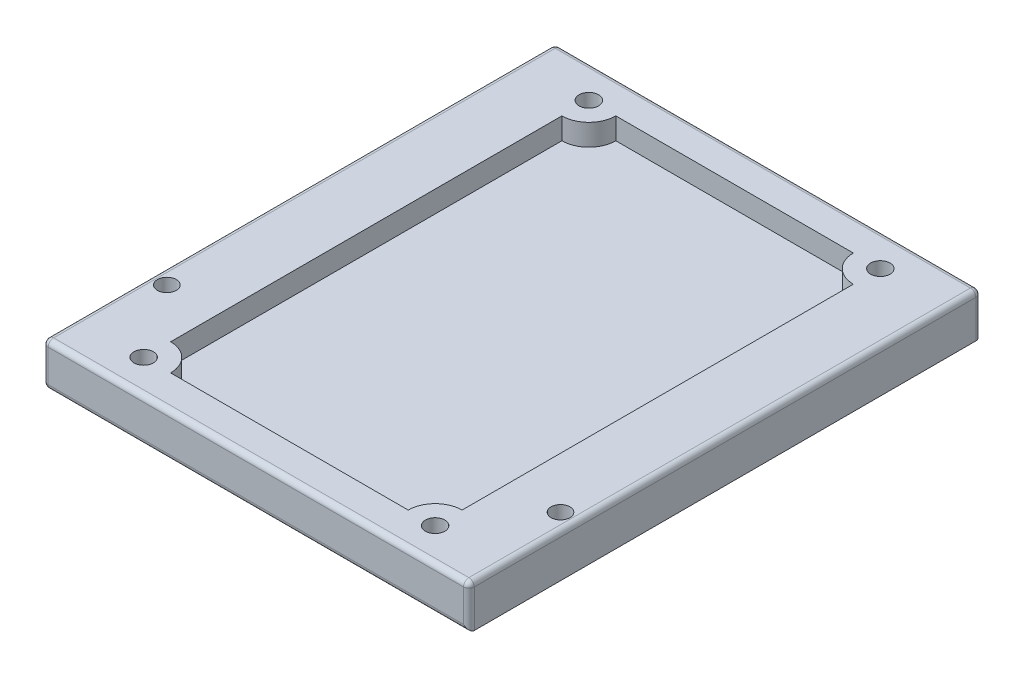
SolidWorks part; units mm, degrees
ref_plane "Front Plane" through (0, 0, 0) normal (0, 0, 1) x (1, 0, 0)
ref_plane "Top Plane" through (0, 0, 0) normal (0, 1, 0) x (1, 0, 0)
ref_plane "Right Plane" through (0, 0, 0) normal (1, 0, 0) x (0, 0, -1)
sketch "Sketch1" plane through (0, 0, 0) normal (0, 1, 0) x (1, 0, 0)
  line L0 (39.5, 95) -> (39.5, 0) construction
  line L1 (0, 0) -> (79, 0)
  line L2 (0, 0) -> (0, 95)
  line L3 (0, 95) -> (79, 95)
  line L4 (79, 0) -> (79, 95)
  circle A0 centre (3, 20) radius 1.75
  circle A1 centre (12.475, 6.225) radius 1.65 construction
  circle A2 centre (12.475, 88.775) radius 1.65 construction
  circle A3 centre (76, 20) radius 1.75
  circle A4 centre (66.525, 6.225) radius 1.65 construction
  circle A5 centre (66.525, 88.775) radius 1.65 construction
  point P20 (39.5, 0)
  dimension "D2" = 3
  dimension "D3" = 3.5
  dimension "D5" = 20
  dimension "D6" = 12.475
  dimension "D7" = 3.3
  dimension "D8" = 12.475
  dimension "D9" = 82.55
  dimension "D10" = 3.3
  dimension "D11" = 6.225
  dimension "D1" = 79
  dimension "D4" = 95
extrude "Boss-Extrude1" add sketch "Sketch1" along normal blind 8
sketch "Sketch3" plane through (0, 0, 0) normal (0, -1, 0) x (1, 0, 0)
  point P0 (12.475, -6.225)
  point P1 (66.525, -6.225)
  point P3 (66.525, -88.775)
  point P5 (12.475, -88.775)
hole_wizard "CBORE for M3 SHCS1" positions "Sketch3" profile "Sketch4" counterbore size "M3" standard "ANSI Metric" end condition through all
sketch "Sketch4" plane through (12.475, 0, -6.225) normal (1, 0, 0) x (0, 0, -1)
  line L0 (0, 0) -> (0, 8)
  line L1 (0, 8) -> (1.8, 8)
  line L3 (1.8, 8) -> (1.8, 3)
  line L4 (1.8, 3) -> (3.25, 3)
  line L5 (3.25, 3) -> (3.25, 0)
  line L7 (3.25, 0) -> (0, 0)
  line L11 (0, -6.35) -> (0, 107.95) construction
  dimension "Thru Hole Dia." = 3.6
  dimension "Thru Hole Depth" = 8
  dimension "C'Bore Dia." = 6.5
  dimension "C'Bore Depth" = 3
sketch "Sketch5" plane through (0, 8, 0) normal (0, 1, 0) x (1, 0, 0)
  line L1 (17.475, 88.775) -> (61.525, 88.775)
  line L2 (12.475, 83.775) -> (12.475, 11.225)
  line L3 (17.475, 6.225) -> (61.525, 6.225)
  line L4 (66.525, 83.775) -> (66.525, 11.225)
  circle A0 centre (12.475, 88.775) radius 1.65 construction
  circle A1 centre (12.475, 6.225) radius 1.65 construction
  arc A3 (12.475, 83.775) -> (17.475, 88.775) centre (12.475, 88.775) ccw
  arc A4 (61.525, 88.775) -> (66.525, 83.775) centre (66.525, 88.775) ccw
  arc A5 (66.525, 11.225) -> (61.525, 6.225) centre (66.525, 6.225) ccw
  arc A6 (17.475, 6.225) -> (12.475, 11.225) centre (12.475, 6.225) ccw
  dimension "D3" = 54.05
  dimension "D1" = 0
  dimension "D2" = 0
extrude "Cut-Extrude1" cut sketch "Sketch5" against normal blind 4
sketch "Sketch6" plane through (0, 0, 0) normal (0, -1, 0) x (1, 0, 0)
  line L1 (9.475, -45) -> (14.475, -45)
  line L2 (9.475, -45) -> (9.475, -65)
  line L3 (9.475, -65) -> (14.475, -65)
  line L4 (14.475, -45) -> (14.475, -65)
  dimension "D1" = 5
  dimension "D2" = 20
  dimension "D3" = 3
  dimension "D4" = 25
extrude "Boss-Extrude2" add sketch "Sketch6" along normal blind 8.8
sketch "Sketch7" plane through (0, 0, -65) normal (0, 0, -1) x (-1, 0, 0)
  line L0 (-14.475, -8.8) -> (-14.475, 0) construction
  line L1 (-9.475, 0) -> (-12.675, 0)
  line L2 (-9.475, 0) -> (-9.475, -6.8)
  line L3 (-9.475, -6.8) -> (-12.675, -6.8)
  line L4 (-12.675, 0) -> (-12.675, -6.8)
  dimension "D1" = 6.8
  dimension "D2" = 1.8
extrude "Cut-Extrude2" cut sketch "Sketch7" against normal through all
fillet "Fillet1" radius 6 1 edges at (14.475, 0, -55) second distance 8 first distance on face at (12.475, 0, -9.475)
fillet "Fillet2" radius 1 10 edges at (0, 4, 0) (39.5, 8, 0) (79, 4, 0) (79, 4, -95) (79, 8, -47.5) (39.5, 8, -95) (0, 4, -95) (0, 8, -47.5) (0, 0, -47.5) (39.5, 0, 0)
